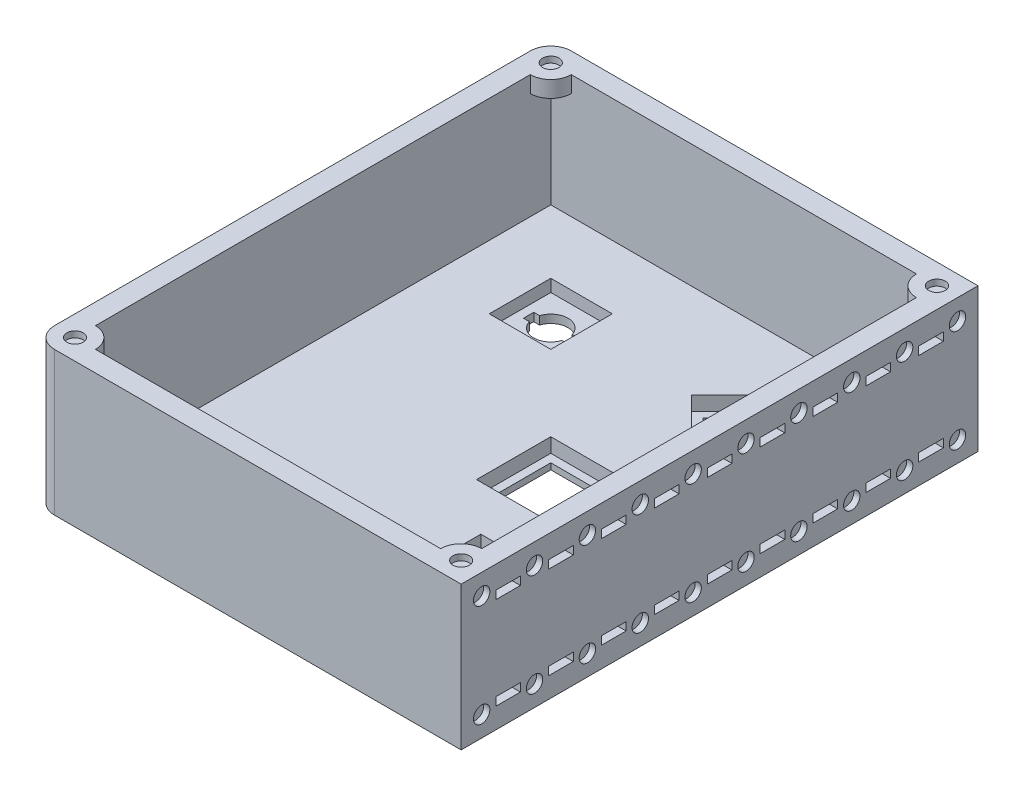
SolidWorks part; units mm, degrees
ref_plane "Front Plane" through (0, 0, 0) normal (0, 0, 1) x (1, 0, 0)
ref_plane "Top Plane" through (0, 0, 0) normal (0, 1, 0) x (1, 0, 0)
ref_plane "Right Plane" through (0, 0, 0) normal (1, 0, 0) x (0, 0, -1)
sketch "Sketch1" plane through (0, 0, 0) normal (0, 1, 0) x (1, 0, 0)
  line L0 (94.15, 127.7999) -> (94.15, -14.5462) construction
  line L1 (0, 0) -> (188.3, 0)
  line L2 (0, 0) -> (0, 116)
  line L3 (0, 116) -> (188.3, 116)
  line L4 (188.3, 0) -> (188.3, 116)
  line L25 (70.05, 108.7604) -> (70.05, 7.0181) construction
  line L26 (50.95, 65.05) -> (65.05, 65.05)
  line L31 (50.95, 65.05) -> (50.95, 50.95)
  line L32 (50.95, 50.95) -> (65.05, 50.95)
  line L33 (27.175, 93) -> (0, 93) construction
  line L34 (23, 88.825) -> (23, 116) construction
  line L35 (65.05, 65.05) -> (65.05, 50.95)
  line L40 (48.45, 67.55) -> (48.45, 48.45)
  line L41 (48.45, 48.45) -> (67.55, 48.45)
  line L42 (67.55, 67.55) -> (67.55, 48.45)
  line L43 (48.45, 67.55) -> (67.55, 67.55)
  line L44 (91.65, 67.55) -> (91.65, 48.45)
  line L45 (91.65, 48.45) -> (72.55, 48.45)
  line L46 (72.55, 67.55) -> (72.55, 48.45)
  line L47 (91.65, 67.55) -> (72.55, 67.55)
  line L48 (89.15, 50.95) -> (75.05, 50.95)
  line L49 (75.05, 65.05) -> (75.05, 50.95)
  line L50 (89.15, 65.05) -> (75.05, 65.05)
  line L51 (89.15, 65.05) -> (89.15, 50.95)
  line L52 (19.2424, 28.9) -> (60.699, 28.9) construction
  line L53 (63, 35.95) -> (77.1, 35.95)
  line L54 (63, 35.95) -> (63, 21.85)
  line L63 (63, 21.85) -> (77.1, 21.85)
  line L64 (-28.1499, 58) -> (157.9099, 58) construction
  line L65 (77.1, 35.95) -> (77.1, 21.85)
  line L66 (51.05, 38.45) -> (89.05, 38.45)
  line L67 (51.05, 38.45) -> (51.05, 19.35)
  line L68 (51.05, 19.35) -> (89.05, 19.35)
  line L69 (89.05, 38.45) -> (89.05, 19.35)
  line L70 (137.25, 19.35) -> (99.25, 19.35)
  line L71 (99.25, 38.45) -> (99.25, 19.35)
  line L72 (137.25, 38.45) -> (99.25, 38.45)
  line L73 (137.25, 38.45) -> (137.25, 19.35)
  line L74 (125.3, 21.85) -> (111.2, 21.85)
  line L75 (111.2, 35.95) -> (111.2, 21.85)
  line L76 (125.3, 35.95) -> (111.2, 35.95)
  line L77 (125.3, 35.95) -> (125.3, 21.85)
  line L78 (99.15, 65.05) -> (99.15, 50.95)
  line L79 (99.15, 65.05) -> (113.25, 65.05)
  line L80 (113.25, 65.05) -> (113.25, 50.95)
  line L81 (99.15, 50.95) -> (113.25, 50.95)
  line L82 (96.65, 48.45) -> (115.75, 48.45)
  line L83 (96.65, 67.55) -> (96.65, 48.45)
  line L84 (96.65, 67.55) -> (115.75, 67.55)
  line L85 (115.75, 67.55) -> (115.75, 48.45)
  line L86 (139.85, 48.45) -> (120.75, 48.45)
  line L87 (139.85, 67.55) -> (139.85, 48.45)
  line L88 (139.85, 67.55) -> (120.75, 67.55)
  line L89 (120.75, 67.55) -> (120.75, 48.45)
  line L90 (137.35, 50.95) -> (123.25, 50.95)
  line L91 (123.25, 65.05) -> (123.25, 50.95)
  line L92 (137.35, 65.05) -> (123.25, 65.05)
  line L93 (137.35, 65.05) -> (137.35, 50.95)
  line L94 (67.55, 53.4595) -> (72.55, 53.4595) construction
  line L95 (91.65, 53.4595) -> (96.65, 53.4595) construction
  line L96 (58, 67.55) -> (58, 101.4303) construction
  line L97 (70.05, 102.9702) -> (60.0798, 93)
  line L102 (60.0798, 93) -> (70.05, 83.0298)
  line L103 (70.05, 83.0298) -> (80.0202, 93)
  line L104 (80.0202, 93) -> (70.05, 102.9702)
  line L109 (81.4344, 93) -> (70.05, 104.3844)
  line L110 (70.05, 104.3844) -> (58.6656, 93)
  line L111 (58.6656, 93) -> (70.05, 81.6156)
  line L112 (70.05, 81.6156) -> (81.4344, 93)
  line L113 (118.25, 81.6156) -> (106.8656, 93)
  line L114 (129.6344, 93) -> (118.25, 81.6156)
  line L115 (118.25, 104.3844) -> (129.6344, 93)
  line L116 (106.8656, 93) -> (118.25, 104.3844)
  line L117 (118.25, 83.0298) -> (108.2798, 93)
  line L118 (128.2202, 93) -> (118.25, 83.0298)
  line L119 (118.25, 102.9702) -> (128.2202, 93)
  line L120 (108.2798, 93) -> (118.25, 102.9702)
  line L121 (-5, 0) -> (-5, 116)
  line L122 (0, 121) -> (188.3, 121)
  line L123 (193.3, 0) -> (193.3, 116)
  line L124 (0, -5) -> (188.3, -5)
  line L125 (193.3, -5) -> (193.3, 121) construction
  line L126 (-5, -5) -> (193.3, -5) construction
  line L127 (-5, 121) -> (193.3, 121) construction
  line L128 (-5, -5) -> (-5, 121) construction
  line L129 (170.7, 91.75) -> (159.9, 91.75)
  line L130 (17.6, 94.25) -> (28.4, 94.25)
  line L131 (17.6, 94.25) -> (17.6, 91.75)
  line L132 (17.6, 91.75) -> (28.4, 91.75)
  line L133 (28.4, 94.25) -> (28.4, 91.75)
  line L134 (159.9, 94.25) -> (159.9, 91.75)
  line L135 (170.7, 94.25) -> (159.9, 94.25)
  line L136 (170.7, 94.25) -> (170.7, 91.75)
  line L137 (23, 93) -> (58, 93) construction
  line L138 (23, 93) -> (23, 58) construction
  line L139 (38, 100.5973) -> (38, 77.6919) construction
  circle A0 centre (23, 93) radius 4.175
  circle A2 centre (23, 93) radius 15
  circle A3 centre (165.3, 93) radius 15
  circle A4 centre (165.3, 93) radius 4.175
  arc A6 (0, 121) -> (-5, 116) centre (0, 116) ccw
  arc A7 (-5, 0) -> (0, -5) centre (0, 0) ccw
  arc A8 (188.3, -5) -> (193.3, 0) centre (188.3, 0) ccw
  arc A9 (193.3, 116) -> (188.3, 121) centre (188.3, 116) ccw
  point P31 (70.05, 35.95)
  point P33 (94.15, 116)
  point P37 (70.05, 38.45)
  point P40 (89.05, 28.9)
  point P41 (77.1, 28.9)
  point P80 (65.05, 58)
  point P91 (188.3, 58)
  point P115 (23, 94.25)
  point P116 (17.6, 93)
  dimension "D3" = 8.35
  dimension "D10" = 5
  dimension "D14" = 30
  dimension "D15" = 20
  dimension "D16" = 126
  dimension "D2" = 2.5
  dimension "D4" = 14.1
  dimension "D5" = 2.5
  dimension "D6" = 5
  dimension "D7" = 19.1
  dimension "D8" = 10.8
  dimension "D9" = 2.5
  dimension "D11" = 38
  dimension "D12" = 10
  dimension "D13" = 1
extrude "Boss-Extrude1" add sketch "Sketch1" against normal blind 5 contours L121 L124 L123 L122 L4 L1 L2 L3 | L1 L4 L3 L2 L113 L116 L115 L114 L84 L85 L82 L83 L40 L43 L42 L41 L47 L44 L45 L46 L66 L69 L68 L67 L72 L73 L70 L71 L89 L88 L87 L86 L112 L111 L110 L109 A2 A3 | A2 A0 | L111 L112 L109 L110 L104 L103 L102 L97 | L116 L113 L114 L115 L117 L120 L119 L118 | A3 A4 | L88 L89 L86 L87 L92 L93 L90 L91 | L85 L84 L83 L82 L81 L78 L79 L80 | L44 L47 L46 L45 L50 L51 L48 L49 | L43 L40 L41 L42 L26 L35 L32 L31 | L69 L66 L67 L68 L53 L65 L63 L54 | L73 L72 L71 L70 L76 L77 L74 L75 region at (94.15, 0, -56.5069) region at (58, 0, -67.2799) region at (91.3799, 0, -58) region at (70.05, 0, -38.0247) region at (118.25, 0, -19.7753) region at (96.9201, 0, -58) region at (130.3, 0, -48.7201) region at (75.5145, 0, -87.5355) region at (112.7855, 0, -87.5355) region at (-2.6506, 0, -58) region at (8.4243, 0, -93) region at (150.7243, 0, -93)
extrude "Boss-Extrude2" add sketch "Sketch1<3>" along normal blind 30 contours L121 L124 L123 L122 L4 L1 L2 L3 region at (-2.6506, 0, -58)
sketch "Sketch1<3>" plane through (0, 0, 0) normal (0, 1, 0) x (1, 0, 0) same geometry as "Sketch1"
sketch "Sketch3" plane through (0, 0, 0) normal (0, 1, 0) x (1, 0, 0)
  line L23 (48.95, 67.05) -> (48.95, 48.95)
  line L24 (48.95, 48.95) -> (67.05, 48.95)
  line L25 (67.05, 48.95) -> (67.05, 67.05)
  line L26 (67.05, 67.05) -> (48.95, 67.05)
  line L27 (48.95, 67.05) -> (48.95, 48.95)
  line L28 (48.95, 48.95) -> (67.05, 48.95)
  line L29 (67.05, 48.95) -> (67.05, 67.05)
  line L30 (67.05, 67.05) -> (48.95, 67.05)
  line L35 (70.05, 105.7986) -> (57.2514, 93)
  line L36 (82.8486, 93) -> (70.05, 105.7986)
  line L37 (70.05, 80.2014) -> (82.8486, 93)
  line L38 (57.2514, 93) -> (70.05, 80.2014)
  line L39 (70.05, 105.7986) -> (57.2514, 93)
  line L40 (82.8486, 93) -> (70.05, 105.7986)
  line L41 (70.05, 80.2014) -> (82.8486, 93)
  line L42 (57.2514, 93) -> (70.05, 80.2014)
  line L47 (61, 37.95) -> (61, 19.85)
  line L48 (61, 19.85) -> (79.1, 19.85)
  line L49 (79.1, 19.85) -> (79.1, 37.95)
  line L50 (79.1, 37.95) -> (61, 37.95)
  line L51 (61, 37.95) -> (61, 19.85)
  line L52 (61, 19.85) -> (79.1, 19.85)
  line L53 (79.1, 19.85) -> (79.1, 37.95)
  line L54 (79.1, 37.95) -> (61, 37.95)
  line L59 (73.05, 67.05) -> (73.05, 48.95)
  line L60 (73.05, 48.95) -> (91.15, 48.95)
  line L61 (91.15, 48.95) -> (91.15, 67.05)
  line L62 (91.15, 67.05) -> (73.05, 67.05)
  line L63 (73.05, 67.05) -> (73.05, 48.95)
  line L64 (73.05, 48.95) -> (91.15, 48.95)
  line L65 (91.15, 48.95) -> (91.15, 67.05)
  line L66 (91.15, 67.05) -> (73.05, 67.05)
  line L71 (97.15, 67.05) -> (97.15, 48.95)
  line L72 (97.15, 48.95) -> (115.25, 48.95)
  line L73 (115.25, 48.95) -> (115.25, 67.05)
  line L74 (115.25, 67.05) -> (97.15, 67.05)
  line L75 (97.15, 67.05) -> (97.15, 48.95)
  line L76 (97.15, 48.95) -> (115.25, 48.95)
  line L77 (115.25, 48.95) -> (115.25, 67.05)
  line L78 (115.25, 67.05) -> (97.15, 67.05)
  line L89 (121.25, 67.05) -> (121.25, 48.95)
  line L90 (121.25, 48.95) -> (139.35, 48.95)
  line L91 (139.35, 48.95) -> (139.35, 67.05)
  line L92 (139.35, 67.05) -> (121.25, 67.05)
  line L93 (121.25, 67.05) -> (121.25, 48.95)
  line L94 (121.25, 48.95) -> (139.35, 48.95)
  line L95 (139.35, 48.95) -> (139.35, 67.05)
  line L96 (139.35, 67.05) -> (121.25, 67.05)
  line L107 (105.4514, 93) -> (118.25, 80.2014)
  line L108 (118.25, 80.2014) -> (131.0486, 93)
  line L109 (131.0486, 93) -> (118.25, 105.7986)
  line L110 (118.25, 105.7986) -> (105.4514, 93)
  line L111 (105.4514, 93) -> (118.25, 80.2014)
  line L112 (118.25, 80.2014) -> (131.0486, 93)
  line L113 (131.0486, 93) -> (118.25, 105.7986)
  line L114 (118.25, 105.7986) -> (105.4514, 93)
  line L119 (109.2, 37.95) -> (109.2, 19.85)
  line L120 (109.2, 19.85) -> (127.3, 19.85)
  line L121 (127.3, 19.85) -> (127.3, 37.95)
  line L122 (127.3, 37.95) -> (109.2, 37.95)
  line L123 (109.2, 37.95) -> (109.2, 19.85)
  line L124 (109.2, 19.85) -> (127.3, 19.85)
  line L125 (127.3, 19.85) -> (127.3, 37.95)
  line L126 (127.3, 37.95) -> (109.2, 37.95)
  dimension "D1" = 2
  dimension "D2" = 2
  dimension "D3" = 2
  dimension "D4" = 2
  dimension "D5" = 2
  dimension "D6" = 2
  dimension "D7" = 2
  dimension "D8" = 2
extrude "Cut-Extrude1" cut sketch "Sketch3" against normal offset from surface (3.5 mm away) 1.5 up to face at (94.15, -5, -58)
sketch "Sketch4" plane through (0, -5, 0) normal (0, -1, 0) x (1, 0, 0)
  line L0 (0, 5) -> (188.3, 5) construction
  line L2 (94.15, 5) -> (257.7491, 5)
  line L3 (94.15, 5) -> (94.15, -159.2792)
  line L4 (94.15, -159.2792) -> (257.7491, -159.2792)
  line L5 (257.7491, 5) -> (257.7491, -159.2792)
extrude "Cut-Extrude2" cut sketch "Sketch4" against normal through all both and the other way through all
sketch "Sketch5" plane through (0, -5, 0) normal (0, -1, 0) x (1, 0, 0)
  line L0 (0, 0) -> (99.15, 0) construction
  line L1 (94.15, 5) -> (99.15, 5)
  line L2 (94.15, 5) -> (94.15, -121)
  line L3 (94.15, -121) -> (99.15, -121)
  line L4 (99.15, 5) -> (99.15, -121)
  dimension "D1" = 5
extrude "Boss-Extrude3" add sketch "Sketch5" against normal up to surface (35 mm away) up to face at (36.4529, 30, -58)
sketch "Sketch8" plane through (0, 30, 0) normal (0, 1, 0) x (1, 0, 0)
  line L0 (0, -5) -> (99.15, -5) construction
  line L1 (0, 121) -> (99.15, 121) construction
  line L2 (-5, 0) -> (-5, 116) construction
  circle A0 centre (0, 0) radius 5
  circle A1 centre (0, 116) radius 5
  circle A2 centre (94.15, 116) radius 5
  circle A3 centre (94.15, 0) radius 5
  circle A4 centre (0, 116) radius 2
  circle A5 centre (94.15, 116) radius 2
  circle A6 centre (94.15, 0) radius 2
  circle A7 centre (0, 0) radius 2
  line M9 (0, 116) -> (94.15, 116)
  line M10 (94.15, 116) -> (94.15, 0)
  line M11 (94.15, 0) -> (0, 0)
  line M12 (0, 0) -> (0, 116)
  arc M15 (0, 121) -> (-5, 116) centre (0, 116) ccw
  arc M17 (-5, 0) -> (0, -5) centre (0, 0) ccw
  dimension "D1" = 4
extrude "Boss-Extrude4" add sketch "Sketch8" against normal blind 4 contours A4 A1 M9 M15 M12 | A4 A1 M12 M9 | A4 M12 M9 | A4 M9 M12 | A5 A2 M10 M9 | A5 M10 M9 | A5 M9 M10 | A5 A2 M9 M10 | A6 A3 M11 M10 | A6 M11 M10 | A6 M10 M11 | A6 A3 M10 M11 | A7 M12 M11 | A7 A0 M12 M17 M11 | A7 M11 M12 | A7 A0 M11 M12 region at (-3.4355, 30, -3.4355) region at (2.3646, 30, -2.3646) region at (-0.2829, 30, 0.2829) region at (0.8488, 30, -0.8488) region at (2.3646, 30, -113.6354) region at (-3.4355, 30, -112.5645) region at (90.65, 30, 0.1414) region at (91.7854, 30, -2.3646) region at (0.8488, 30, -115.1512) region at (-0.2829, 30, -116.2829) region at (94.4329, 30, 0.2829) region at (93.3012, 30, -0.8488) region at (91.7854, 30, -113.6354) region at (94.15, 30, -120.8586) region at (93.3012, 30, -115.1512) region at (94.4329, 30, -116.2829)
extrude "Cut-Extrude5" cut sketch "Sketch8<3>" against normal blind 1.5 contours A7 M12 M11 | A7 M11 M12 | A4 M9 M12 | A4 M12 M9 | A5 M10 M9 | A5 M9 M10 | A6 M11 M10 | A6 M10 M11 region at (0.8488, 30, -0.8488) region at (-0.2829, 30, 0.2829) region at (94.4329, 30, 0.2829) region at (93.3012, 30, -0.8488) region at (0.8488, 30, -115.1512) region at (-0.2829, 30, -116.2829) region at (94.4329, 30, -116.2829) region at (93.3012, 30, -115.1512)
sketch "Sketch8<3>" plane through (0, 30, 0) normal (0, 1, 0) x (1, 0, 0) same geometry as "Sketch8"
sketch "Sketch9" plane through (0, 0, 0) normal (0, 1, 0) x (1, 0, 0)
  line L0 (17.6, 94.25) -> (17.6, 91.75) construction
  line L1 (15.5, 100.5) -> (30.5, 100.5)
  line L2 (15.5, 100.5) -> (15.5, 85.5)
  line L3 (15.5, 85.5) -> (30.5, 85.5)
  line L4 (30.5, 100.5) -> (30.5, 85.5)
  arc A0 (26.9835, 94.25) -> (19.0165, 94.25) centre (23, 93) ccw construction
  point P6 (17.6, 93)
  point P7 (15.5, 93)
  point P11 (23, 97.175)
  point P12 (23, 100.5)
  dimension "D1" = 15
extrude "Cut-Extrude6" cut sketch "Sketch9" against normal offset from surface (3 mm away) 2 up to face at (31.0382, -5, -58)
sketch "Sketch11" plane through (99.15, 0, 0) normal (1, 0, 0) x (0, 0, -1)
  line L0 (58, 30) -> (58, -5) construction
  line L1 (121, 30) -> (-5, 30) construction
  line L2 (121, -5) -> (-5, -5) construction
  line L3 (121, 30) -> (121, -5) construction
  line L4 (121, 12.5) -> (-5, 12.5) construction
  line L5 (-5, 30) -> (-5, -5) construction
  circle A0 centre (0, 0) radius 2
  point P12 (0, 0)
  point P15 (0, 0)
  point P17 (0, 0)
  point P18 (0, 0)
  point P19 (0, 0)
  dimension "D1" = 4
extrude "Cut-Extrude7" cut sketch "Sketch11" against normal blind 1.5
pattern_linear "LPattern1" count 10 spacing 12.8889 along (0, 0, -1) count 2 spacing 25 along (0, 1, 0) of "Cut-Extrude7"
sketch "Sketch12" plane through (99.15, 0, 0) normal (1, 0, 0) x (0, 0, -1)
  line L0 (6.4444, 35.4938) -> (6.4444, -7.6948) construction
  line L1 (3.4444, 0) -> (9.4444, 0)
  line L2 (3.4444, 0) -> (3.4444, 2)
  line L3 (3.4444, 2) -> (9.4444, 2)
  line L4 (9.4444, 0) -> (9.4444, 2)
  line L5 (0, 0) -> (12.8889, 0) construction
  line L6 (116, 0) -> (0, 0) construction
  point P6 (6.4444, 2)
  point P7 (6.4444, 0)
  dimension "D1" = 6
  dimension "D2" = 2
  dimension "D3" = 12.8889
extrude "Cut-Extrude8" cut sketch "Sketch12" against normal up to surface (5 mm away) up to face at (94.15, 20.5, -58)
pattern_linear "LPattern2" count 9 spacing 12.8889 along (0, 0, -1) count 2 spacing 22.5 along (0, 1, 0) of "Cut-Extrude8"
equation "\"Hole Spacing\"= \"D3@Sketch12\""
equation "\"D3@LPattern2\"=\"Hole Spacing\""
